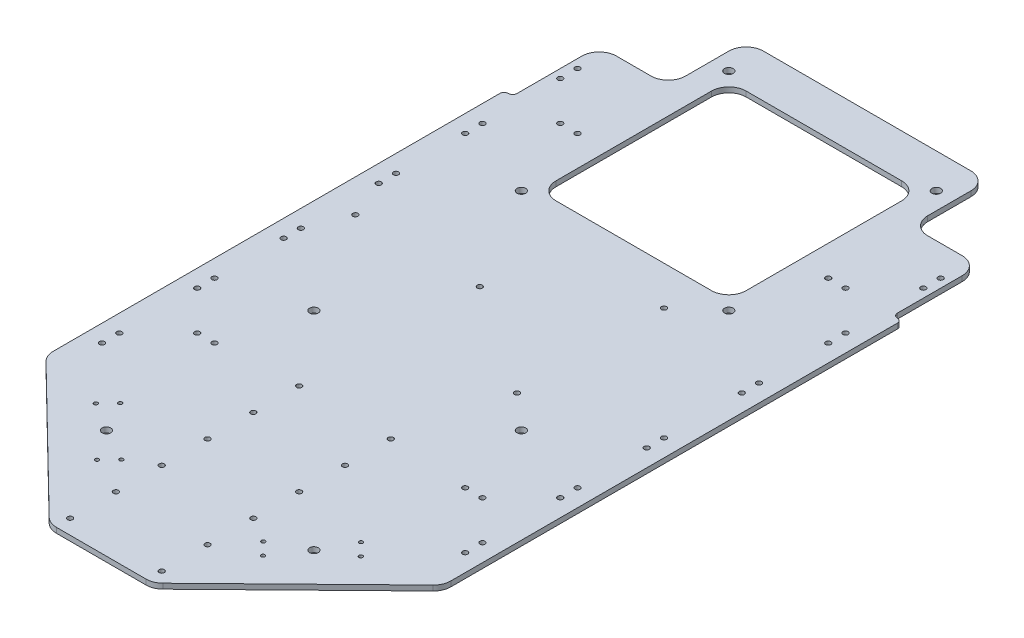
SolidWorks part; units mm, degrees
material "Acrylic (Medium-high impact)"
ref_plane "Спереди" through (0, 0, 0) normal (0, 0, 1) x (1, 0, 0)
ref_plane "Сверху" through (0, 0, 0) normal (0, 1, 0) x (1, 0, 0)
ref_plane "Справа" through (0, 0, 0) normal (1, 0, 0) x (0, 0, -1)
sketch "Эскиз1" plane through (0, 0, 0) normal (0, 1, 0) x (1, 0, 0)
  line L0 (0, 0) -> (0, 50000) construction
  line L1 (115, -200) -> (-115, -200)
  line L2 (115, -200) -> (115, 200)
  line L3 (115, 200) -> (-115, 200)
  line L4 (-115, -200) -> (-115, 200)
  line L5 (115, -200) -> (-115, 200) construction
  line L6 (115, 200) -> (-115, -200) construction
  line L7 (0, 0) -> (50000, 0) construction
  line L8 (-155.9021, -120) -> (49844.0979, -120) construction
  circle A0 centre (-60, -180) radius 2.5
  circle A1 centre (60, -180) radius 2.5
  circle A4 centre (60, -60) radius 2.5
  circle A5 centre (-60, -60) radius 2.5
  circle A6 centre (-60, 180) radius 2.5
  circle A7 centre (60, 180) radius 2.5
  circle A8 centre (60, 60) radius 2.5
  circle A9 centre (-60, 60) radius 2.5
  point P0 (0, 0)
  dimension "D3" = 5
  dimension "D1" = 400
  dimension "D2" = 230
  dimension "D4" = 60
  dimension "D5" = 60
  dimension "D6" = 120
extrude "Бобышка-Вытянуть1" add sketch "Эскиз1" along normal blind 3
sketch "Sketch1" plane through (0, 3, 0) normal (0, 1, 0) x (1, 0, 0)
  line L0 (-105, 67.3123) -> (-105, 50067.3123) construction
  line L1 (-110, -110) -> (110, -110) construction
  line L2 (-110, -110) -> (-110, 110) construction
  line L3 (-110, 110) -> (110, 110) construction
  line L4 (110, -110) -> (110, 110) construction
  line L5 (-110, -110) -> (110, 110) construction
  line L6 (-110, 110) -> (110, -110) construction
  line L7 (-132.5439, 105) -> (49867.4561, 105) construction
  line L8 (0, 0) -> (0, 50000) construction
  line L9 (0, 0) -> (50000, 0) construction
  circle A0 centre (-105, 82.5) radius 1.5
  circle A1 centre (-105, 72.5) radius 1.5
  circle A2 centre (-82.5, 105) radius 1.5
  circle A3 centre (-72.5, 105) radius 1.5
  circle A4 centre (82.5, 105) radius 1.5
  circle A5 centre (72.5, 105) radius 1.5
  circle A6 centre (105, 82.5) radius 1.5
  circle A7 centre (105, 72.5) radius 1.5
  circle A8 centre (105, -82.5) radius 1.5
  circle A9 centre (105, -72.5) radius 1.5
  circle A10 centre (82.5, -105) radius 1.5
  circle A11 centre (72.5, -105) radius 1.5
  circle A12 centre (-82.5, -105) radius 1.5
  circle A13 centre (-72.5, -105) radius 1.5
  circle A14 centre (-105, -82.5) radius 1.5
  circle A15 centre (-105, -72.5) radius 1.5
  circle A16 centre (-105, 137.5) radius 1.5
  circle A17 centre (-105, 127.5) radius 1.5
  circle A18 centre (105, 127.5) radius 1.5
  circle A19 centre (105, 137.5) radius 1.5
  circle A20 centre (105, -127.5) radius 1.5
  circle A21 centre (105, -137.5) radius 1.5
  circle A22 centre (-105, -127.5) radius 1.5
  circle A23 centre (-105, -137.5) radius 1.5
  point P0 (0, 0)
  dimension "D4" = 3
  dimension "D1" = 220
  dimension "D2" = 220
  dimension "D3" = 5
  dimension "D5" = 27.5
  dimension "D6" = 10
  dimension "D8" = 5
  dimension "D7" = 4
extrude "Tower holes" cut sketch "Sketch1" against normal through all
sketch "Sketch2" plane through (0, 3, 0) normal (0, 1, 0) x (1, 0, 0)
  line L0 (0, 0) -> (0, 50000) construction
  line L1 (-115, 200) -> (-70, 200)
  line L2 (-115, 200) -> (-115, 155)
  line L3 (-110, 155) -> (-70, 155)
  line L4 (-70, 200) -> (-70, 155)
  line L5 (70, 200) -> (70, 155)
  line L6 (110, 155) -> (70, 155)
  line L7 (115, 200) -> (115, 155)
  line L8 (115, 200) -> (70, 200)
  line L9 (110, 155) -> (110, 105)
  line L11 (-115, 155) -> (-115, 105)
  line L12 (-115, 105) -> (-110, 105)
  line L13 (-110, 155) -> (-110, 105)
  line L14 (115, 105) -> (110, 105)
  line L15 (115, 155) -> (115, 105)
  dimension "D1" = 45
  dimension "D2" = 50
  dimension "D3" = 5
  dimension "D4" = 50
extrude "Cut-Extrude2" cut sketch "Sketch2" against normal blind 7
sketch "Sketch3" plane through (0, 3, 0) normal (0, 1, 0) x (1, 0, 0)
  line L0 (-60, 60) -> (49940, 60) construction
  line L1 (55, 65) -> (-55, 65)
  line L2 (55, 65) -> (55, 175)
  line L3 (55, 175) -> (-55, 175)
  line L4 (-55, 65) -> (-55, 175)
  line L5 (55, 65) -> (-55, 175) construction
  line L6 (55, 175) -> (-55, 65) construction
  point P0 (0, 120)
  dimension "D1" = 110
  dimension "D2" = 60
extrude "Cut-Extrude3" cut sketch "Sketch3" against normal through all
fillet "Fillet1" radius 10 4 edges at (-55, 1.5, -65) (55, 1.5, -65) (55, 1.5, -175) (-55, 1.5, -175)
fillet "Fillet2" radius 10 6 edges at (70, 1.5, -155) (70, 1.5, -200) (-70, 1.5, -155) (-70, 1.5, -200) (-110, 1.5, -155) (110, 1.5, -155)
sketch "Sketch4" plane through (0, 0, 0) normal (0, 1, 0) x (1, 0, 0)
  line L0 (-115, -200) -> (115, -200) construction
  line L1 (100, -200) -> (-100, -200)
  line L2 (100, -200) -> (100, -243)
  line L3 (100, -243) -> (-100, -243)
  line L4 (-100, -200) -> (-100, -243)
  line L5 (0, -200) -> (0, 49800) construction
  point P6 (0, -243)
  point P10 (0, -200)
  dimension "D1" = 43
  dimension "D2" = 200
extrude "Boss-Extrude1" add sketch "Sketch4" along normal blind 3
sketch "Sketch5" plane through (0, 3, 0) normal (0, 1, 0) x (1, 0, 0)
  line L0 (0, -209) -> (0, 49791) construction
  line L1 (-100, -243) -> (100, -243) construction
  line L2 (60, -180) -> (-49940, -180) construction
  line L3 (26.5, -208) -> (-49973.5, -208) construction
  circle A7 centre (26.5, -208) radius 1.5
  circle A8 centre (-26.5, -208) radius 1.5
  circle A9 centre (26.5, -234.5) radius 1.5
  circle A10 centre (-26.5, -234.5) radius 1.5
  circle A11 centre (26.5, -181.5) radius 1.5
  circle A12 centre (-26.5, -181.5) radius 1.5
  circle A13 centre (26.5, -155) radius 1.5
  circle A14 centre (-26.5, -155) radius 1.5
  circle A15 centre (26.5, -128.5) radius 1.5
  circle A16 centre (-26.5, -128.5) radius 1.5
  circle A17 centre (26.5, -102) radius 1.5
  circle A18 centre (-26.5, -102) radius 1.5
  point P4 (0, -243)
  dimension "D2" = 26.5
  dimension "D3" = 3
  dimension "D1" = 28
  dimension "D4" = 2
  dimension "D5" = 2
  dimension "D6" = 4
extrude "Cut-Extrude4" cut sketch "Sketch5" against normal through all
sketch "Sketch6" plane through (0, 3, 0) normal (0, 1, 0) x (1, 0, 0)
  line L0 (115, -160) -> (30, -243)
  line L1 (-100, -243) -> (100, -243) construction
  line L2 (-115, -160) -> (-30, -243)
  line L4 (115, -243) -> (30, -243)
  line L7 (-115, 105) -> (-115, -200) construction
  line L8 (115, -200) -> (115, 105) construction
  line L9 (-30, -243) -> (-115, -243)
  line L10 (-115, -243) -> (-115, -160)
  line L11 (115, -243) -> (115, -160)
  dimension "D1" = 60
  dimension "D2" = 83
extrude "Cut-Extrude5" cut sketch "Sketch6" against normal through all
fillet "Fillet3" radius 10 4 edges at (-30, 1.5, 243) (30, 1.5, 243) (-115, 1.5, 160) (115, 1.5, 160)
fillet "Fillet4" radius 2.5 4 edges at (115, 1.5, -105) (110, 1.5, -105) (-110, 1.5, -105) (-115, 1.5, -105)
sketch "Sketch7" plane through (0, 3, 0) normal (0, 1, 0) x (1, 0, 0)
  line L0 (-25.9274, -243) -> (25.9274, -243) construction
  line L1 (41.0274, -190.3) -> (35814.7285, 34741.6669) construction
  line L2 (111.9864, -162.9427) -> (32.9138, -240.1547) construction
  line L3 (55.3369, -176.3272) -> (-34876.63, 35597.3738) construction
  line L4 (54.9069, -183.7355) -> (35828.6079, 34748.2314) construction
  line L5 (0, -243) -> (0, 49757) construction
  circle A0 centre (41.0274, -190.3) radius 1.1
  circle A1 centre (48.0138, -197.4547) radius 1.1
  circle A2 centre (76.6328, -169.5092) radius 1.1
  circle A3 centre (69.6464, -162.3544) radius 1.1
  circle A4 centre (-69.6464, -162.3544) radius 1.1
  circle A5 centre (-76.6328, -169.5092) radius 1.1
  circle A6 centre (-48.0138, -197.4547) radius 1.1
  circle A7 centre (-41.0274, -190.3) radius 1.1
  point P21 (0, -243)
  dimension "D1" = 2.2
  dimension "D2" = 52.7
  dimension "D3" = 15.1
  dimension "D4" = 5
  dimension "D5" = 20
extrude "Cut-Extrude6" cut sketch "Sketch7" against normal through all
sketch "Sketch8" plane through (0, 3, 0) normal (0, 1, 0) x (1, 0, 0)
  line L0 (115, -155.788) -> (115, 102.5) construction
  line L1 (105, -72.5) -> (50105, -72.5) construction
  line L2 (97.5264, -27.5) -> (50097.5264, -27.5) construction
  line L3 (105, -72.5) -> (105, 72.5) construction
  line L4 (105, 0) -> (50105, 0) construction
  line L5 (0, 0) -> (0, 50000) construction
  circle A0 centre (105, -32.5) radius 1.5
  circle A1 centre (105, -22.5) radius 1.5
  circle A2 centre (105, 22.5) radius 1.5
  circle A3 centre (105, 32.5) radius 1.5
  circle A4 centre (-105, 32.5) radius 1.5
  circle A5 centre (-105, 22.5) radius 1.5
  circle A6 centre (-105, -22.5) radius 1.5
  circle A7 centre (-105, -32.5) radius 1.5
  point P16 (105, 0)
  dimension "D1" = 3
  dimension "D2" = 10
  dimension "D3" = 40
  dimension "D4" = 5
extrude "Cut-Extrude7" cut sketch "Sketch8" against normal through all
sketch "Sketch9" plane through (0, 3, 0) normal (0, 1, 0) x (1, 0, 0)
  line L0 (45.4682, 0) -> (-2949.023, 0) construction
  circle A0 centre (40, 42.5) radius 1.5
  circle A1 centre (40, -42.5) radius 1.5
  dimension "D2" = 3
  dimension "D1" = 42.5
  dimension "D3" = 40
extrude "NUC holes" cut sketch "Sketch9" against normal through all
sketch "Sketch10" plane through (0, 3, 0) normal (0, 1, 0) x (1, 0, 0)
  line L0 (-60, -8.4603) -> (-60, 49991.5397) construction
  circle A0 centre (-96, 0) radius 1.5
  circle A1 centre (-24, 0) radius 1.5
  dimension "D2" = 3
  dimension "D1" = 36
  dimension "D3" = 60
extrude "Lidar box holes" cut sketch "Sketch10" against normal through all
equation "\"camera plate width\"=220"
equation "\"camera plate length\"=220"
equation "\"camera height\"= 100"
equation "\"zero height\"= 100"
equation "\"D1@Sketch1\"=\"camera plate length\""
